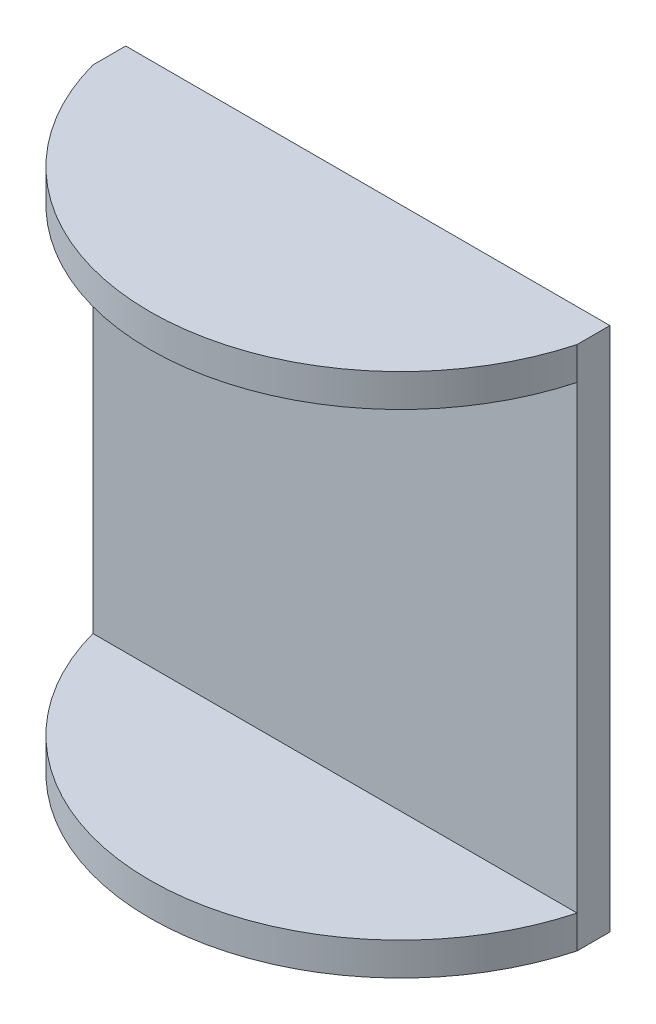
SolidWorks part; units mm, degrees
material "Pine"
ref_plane "Front Plane" through (0, 0, 0) normal (0, 0, 1) x (1, 0, 0)
ref_plane "Top Plane" through (0, 0, 0) normal (0, 1, 0) x (1, 0, 0)
ref_plane "Right Plane" through (0, 0, 0) normal (1, 0, 0) x (0, 0, -1)
sketch "Sketch2" plane through (0, 0, 0) normal (0, 1, 0) x (1, 0, 0)
  line L0 (-37.465, 0) -> (37.465, 0)
  arc A0 (-37.465, 0) -> (37.465, 0) centre (0, 10.16) ccw
  point P3 (0, 13.15)
  point P4 (0, 0)
  point P6 (0, 8.5185)
  dimension "D2" = 10.16
  dimension "D1" = 74.93
extrude "Boss-Extrude1" add sketch "Sketch2" along normal blind 5.08
sketch "Sketch3" plane through (0, 5.08, 0) normal (0, 1, 0) x (1, 0, 0)
  line L0 (-37.465, 0) -> (-37.465, 5.08)
  line L1 (-37.465, 0) -> (37.465, 0)
  line L2 (-37.465, 5.08) -> (37.465, 5.08)
  line L3 (37.465, 0) -> (37.465, 5.08)
  line L4 (37.465, 0) -> (-37.465, 0) construction
  arc A0 (-37.465, 0) -> (37.465, 0) centre (0, 10.16) ccw construction
  point P0 (37.465, 0)
  dimension "D1" = 5.08
extrude "Boss-Extrude2" add sketch "Sketch3" against normal up to vertex (5.08 mm away) and the other way blind 76.2 up to point (-37.465, 0, 0)
sketch "Sketch4" plane through (0, 81.28, 0) normal (0, 1, 0) x (1, 0, 0)
  line L0 (-37.465, 0) -> (37.465, 0)
  line L1 (37.465, 0) -> (-37.465, 0) construction
  line L2 (-37.465, 0) -> (37.465, 0) construction
  arc A0 (-37.465, 0) -> (37.465, 0) centre (0, 10.16) ccw
  point P8 (37.465, 0)
  dimension "D1" = 10.16
extrude "Boss-Extrude3" add sketch "Sketch4" against normal blind 5.08
